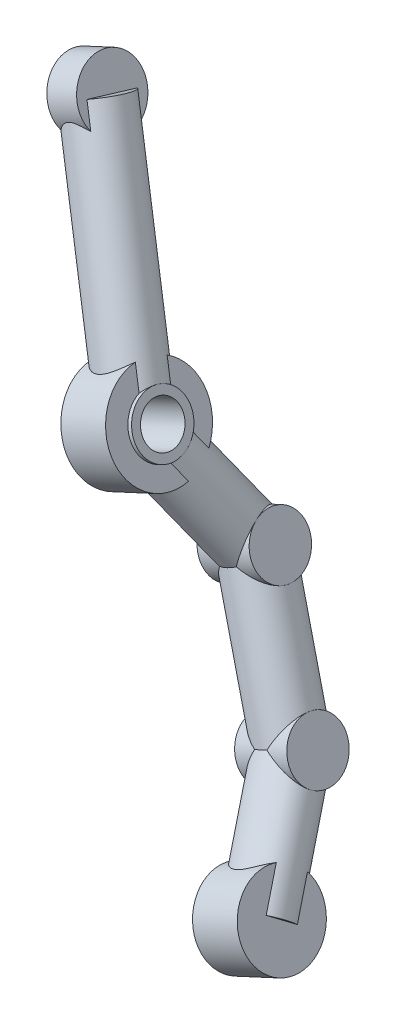
SolidWorks part; units mm, degrees
material "6061-T6 (SS)"
ref_plane "Alzado" through (0, 0, 0) normal (0, 0, 1) x (1, 0, 0)
ref_plane "Planta" through (0, 0, 0) normal (0, 1, 0) x (1, 0, 0)
ref_plane "Vista lateral" through (0, 0, 0) normal (1, 0, 0) x (0, 0, -1)
sketch3d "Sk_Brazo_1"
  line L0 (424.6109, 411.5791, -33) -> (436.398, 386.181, -26)
  dimension "D1" = 28.8617
sweep "Brazo_1" add path "Sk_Brazo_1" circular profile diameter 7 parameters "D3"=7
sketch3d "Sk_Brazo_2"
  line L0 (436.398, 386.181, -26) -> (442.7125, 372.5749, -34)
  dimension "D1" = 17
sweep "Brazo_2" add path "Sk_Brazo_2" circular profile diameter 7 parameters "D3"=7
sketch3d "Sk_Brazo_3"
  line L0 (442.7125, 372.5749, -34) -> (450.2899, 356.2475, -31)
  dimension "D1" = 18.2483
sweep "Brazo_3" add path "Sk_Brazo_3" circular profile diameter 7 parameters "D3"=7
sketch3d "Sk_Brazo_4"
  line L0 (450.2899, 356.2475, -31) -> (455.3416, 345.3626, -22)
  dimension "D1" = 15
sweep "Brazo_4" add path "Sk_Brazo_4" circular profile diameter 7 parameters "D3"=7
sketch3d "Sk_Brazo_codo_1"
  line L0 (433.2232, 384.7076, -26) -> (439.5728, 387.6544, -26)
  dimension "D1" = 7
sweep "Brazo_codo_1" add path "Sk_Brazo_codo_1" circular profile diameter 7 parameters "D3"=7
sketch3d "Sk_Brazo_codo_2"
  line L0 (439.5378, 371.1015, -34) -> (445.8873, 374.0483, -34)
  dimension "D1" = 7
sweep "Brazo_codo_2" add path "Sk_Brazo_codo_2" circular profile diameter 7 parameters "D3"=7
sketch3d "Sk_Brazo_codo_3"
  line L0 (447.1152, 354.7741, -31) -> (453.4647, 357.7209, -31)
  dimension "D1" = 7
sweep "Brazo_codo_3" add path "Sk_Brazo_codo_3" circular profile diameter 7 parameters "D3"=7
sketch3d "Sk_Ojo_pivote"
  line L0 (433.6768, 384.9181, -26) -> (439.1192, 387.4439, -26)
  dimension "D1" = 6
sweep "Ojo_pivote" add path "Sk_Ojo_pivote" circular profile diameter 12 parameters "D3"=12
sketch3d "Sk_Anclaje_cable"
  line L0 (422.7967, 410.7372, -33) -> (426.425, 412.4211, -33)
  dimension "D1" = 4
sweep "Anclaje_cable" add path "Sk_Anclaje_cable" circular profile diameter 8 parameters "D3"=8
sketch3d "Sk_Ojo_zapata"
  line L0 (452.6203, 344.0997, -22) -> (458.0628, 346.6255, -22)
  dimension "D1" = 6
sweep "Ojo_zapata" add path "Sk_Ojo_zapata" circular profile diameter 10 parameters "D3"=10
sketch3d "Sk_Taladro_pivote"
  line L0 (432.7697, 384.4971, -26) -> (440.0263, 387.8649, -26)
  dimension "D1" = 8
sweep "Taladro_pivote" cut path "Sk_Taladro_pivote" circular profile diameter 5 parameters "D3"=5
